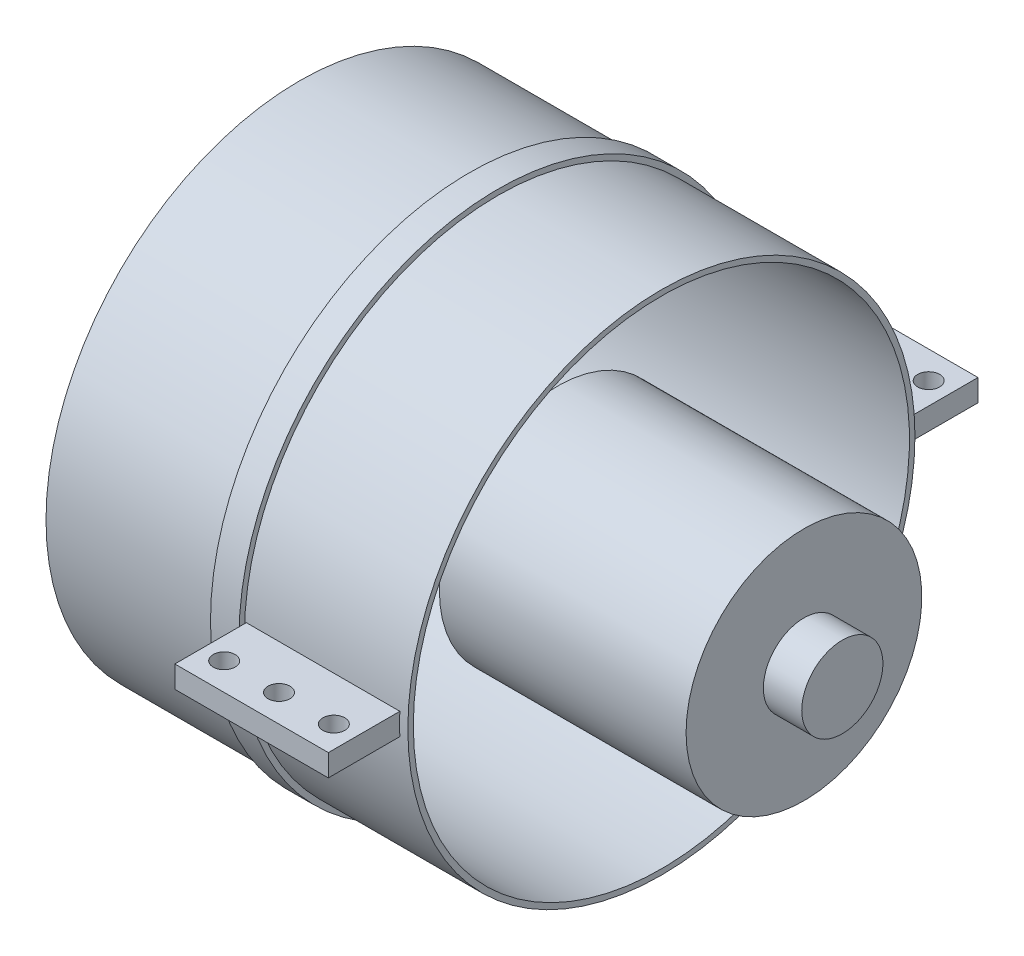
SolidWorks part; units mm, degrees
ref_plane "Front Plane" through (0, 0, 0) normal (0, 0, 1) x (1, 0, 0)
ref_plane "Top Plane" through (0, 0, 0) normal (0, 1, 0) x (1, 0, 0)
ref_plane "Right Plane" through (0, 0, 0) normal (1, 0, 0) x (0, 0, -1)
sketch "Sketch1" plane through (0, 0, 0) normal (0, 1, 0) x (1, 0, 0)
  line L0 (0, 45.25) -> (0, 46.25)
  line L1 (0, 46.25) -> (31, 46.25)
  line L2 (31, 46.25) -> (31, 47.25)
  line L3 (31, 47.25) -> (36.2, 47.25)
  line L4 (36.2, 47.25) -> (36.2, 46.25)
  line L5 (36.2, 46.25) -> (66, 46.25)
  line L6 (66, 46.25) -> (66, 45.25)
  line L7 (66, 45.25) -> (0, 45.25)
  line L8 (0, 0) -> (50000, 0) construction
  line L9 (47, 21.5) -> (92, 21.5)
  line L10 (92, 21.5) -> (92, 7.4)
  line L11 (92, 7.4) -> (99, 7.4)
  line L12 (99, 7.4) -> (99, 0)
  line L13 (99, 0) -> (47, 0)
  line L14 (47, 0) -> (47, 21.5)
  dimension "D1" = 46.25
  dimension "D2" = 1
  dimension "D3" = 31
  dimension "D4" = 5.2
  dimension "D5" = 1
  dimension "D6" = 66
  dimension "D7" = 21.5
  dimension "D8" = 7.4
  dimension "D9" = 7
  dimension "D10" = 26
  dimension "D11" = 45
revolve "Revolve1" add sketch "Sketch1" angle 360 about L8
ref_axis "Axis1" through (173.0989, 0, 0) along (-1, 0, 0)
sketch "Sketch2" plane through (66, 0, 0) normal (1, 0, 0) x (0, 0, -1)
  line L0 (46.2067, -2) -> (59.25, -2)
  line L1 (59.25, -2) -> (59.25, 2)
  line L2 (59.25, 2) -> (46.2067, 2)
  line L3 (0, 0) -> (50000, 0) construction
  circle A0 centre (0, 0) radius 46.25 construction
  arc A1 (46.2067, 2) -> (46.2067, -2) centre (0, 0) cw
  dimension "D1" = 4
  dimension "D2" = 59.25
extrude "Boss-Extrude1" add sketch "Sketch2" against normal blind 28 from offset 1.5 offset against normal yes
sketch "Sketch3" plane through (0, 2, 0) normal (0, 1, 0) x (1, 0, 0)
  line L0 (60.5, 54.25) -> (40.5, 54.25) construction
  line L3 (50.5, 54.25) -> (50.5, 58.1661) construction
  line L4 (64.5, 59.25) -> (64.5, 46.2067) construction
  line L5 (36.5, 59.25) -> (36.5, 46.2067) construction
  line L6 (120.765, 0) -> (0, 0) construction
  circle A0 centre (60.5, 54.25) radius 2
  circle A1 centre (50.5, 54.25) radius 2
  circle A2 centre (40.5, 54.25) radius 2
  dimension "D1" = 4
  dimension "D2" = 20
  dimension "D3" = 54.25
extrude "Cut-Extrude1" cut sketch "Sketch3" against normal through all
pattern_circular "CirPattern1" count 2 every 180 about axis through (173.0989, 0, 0) along (-1, 0, 0) of "Boss-Extrude1", "Cut-Extrude1"
